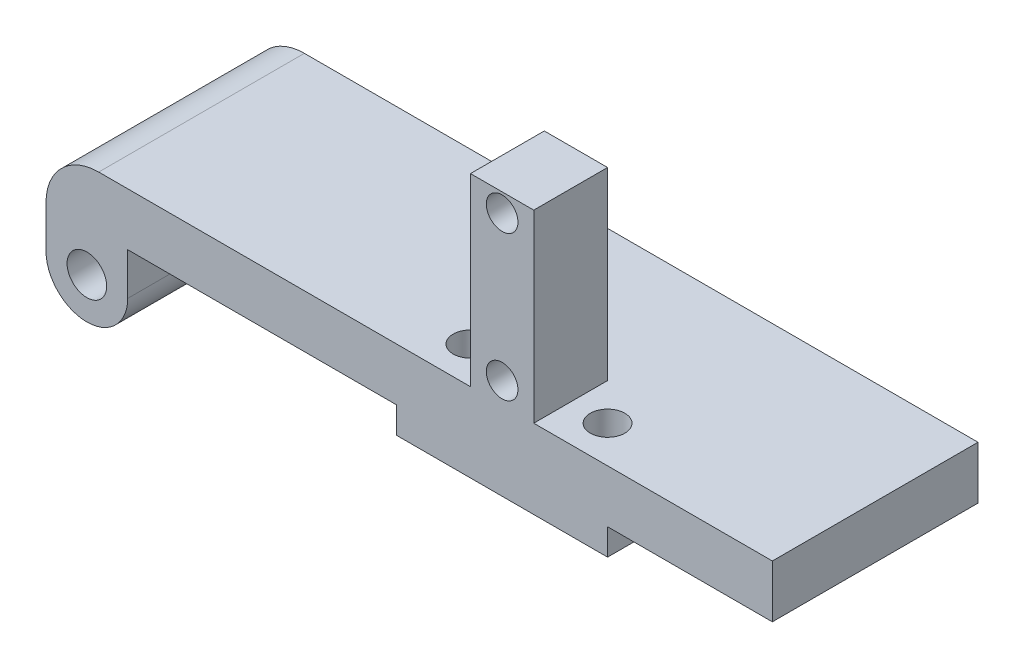
SolidWorks part; units mm, degrees
ref_plane "Front Plane" through (0, 0, 0) normal (0, 0, 1) x (1, 0, 0)
ref_plane "Top Plane" through (0, 0, 0) normal (0, 1, 0) x (1, 0, 0)
ref_plane "Right Plane" through (0, 0, 0) normal (1, 0, 0) x (0, 0, -1)
sketch "Sketch1" plane through (0, 0, 0) normal (0, 0, 1) x (1, 0, 0)
  line L0 (-37.3856, -8.255) -> (-37.3856, -3.175)
  line L1 (-37.3856, 3.175) -> (37.3856, 3.175)
  line L2 (-37.3856, 3.175) -> (-37.3856, -3.175)
  line L3 (-27.5431, -3.175) -> (37.3856, -3.175)
  line L4 (37.3856, 3.175) -> (37.3856, -3.175)
  line L5 (-37.3856, 3.175) -> (37.3856, -3.175) construction
  line L6 (-37.3856, -3.175) -> (37.3856, 3.175) construction
  line L7 (-27.5431, -8.255) -> (-27.5431, -3.175)
  circle A0 centre (-32.4644, -8.255) radius 2.3812
  arc A1 (-37.3856, -8.255) -> (-27.5431, -8.255) centre (-32.4644, -8.255) ccw
  point P0 (0, 0)
  dimension "D1" = 4.7625
  dimension "D3" = 2.54
  dimension "D2" = 6.35
  dimension "D4" = 69.85
  dimension "D5" = 5.08
extrude "Boss-Extrude1" add sketch "Sketch1" along normal blind 38.1
fillet "Fillet1" radius 6.35 1 edges at (-37.3856, 3.175, 19.05)
sketch "Sketch3" plane through (37.3856, 0, 0) normal (1, 0, 0) x (0, 0, -1)
  line L4 (0, -3.175) -> (0, 3.175)
  line L5 (0, 3.175) -> (-38.1, 3.175)
  line L6 (-38.1, 3.175) -> (-38.1, -3.175)
  line L7 (-38.1, -3.175) -> (0, -3.175)
  line L8 (0, -3.175) -> (0, 3.175)
  line L9 (0, 3.175) -> (-38.1, 3.175)
  line L10 (-38.1, 3.175) -> (-38.1, -3.175)
  line L11 (-38.1, -3.175) -> (0, -3.175)
  dimension "D1" = 0
extrude "Boss-Extrude2" add sketch "Sketch3" along normal blind 12.7
sketch "Sketch2" plane through (0, 3.175, 0) normal (0, 1, 0) x (1, 0, 0)
  line L1 (48.4981, -15.875) -> (11.9856, -15.875) construction
  line L2 (48.4981, -15.875) -> (48.4981, 0) construction
  line L3 (48.4981, 0) -> (11.9856, 0) construction
  line L4 (11.9856, -15.875) -> (11.9856, 0) construction
  line L5 (48.4981, -15.875) -> (11.9856, 0) construction
  line L6 (48.4981, 0) -> (11.9856, -15.875) construction
  line L7 (11.9856, -17.4625) -> (-16.5894, -17.4625) construction
  line L8 (11.9856, -17.4625) -> (11.9856, 1.5875) construction
  line L9 (11.9856, 1.5875) -> (-16.5894, 1.5875) construction
  line L10 (-16.5894, -17.4625) -> (-16.5894, 1.5875) construction
  line L11 (11.9856, -17.4625) -> (-16.5894, 1.5875) construction
  line L12 (11.9856, 1.5875) -> (-16.5894, -17.4625) construction
  line L13 (37.3856, -25.4) -> (37.3856, 9.525) construction
  line L14 (50.0856, 0) -> (-31.0356, 0) construction
  line L15 (-34.8456, -38.1) -> (-30.0831, -38.1) construction
  line L16 (-34.8456, -38.1) -> (-30.0831, -38.1) construction
  line L18 (21.3519, -24.765) -> (13.7319, -24.765)
  line L19 (21.3519, -24.765) -> (21.3519, -15.875)
  line L20 (21.3519, -15.875) -> (13.7319, -15.875)
  line L21 (13.7319, -24.765) -> (13.7319, -15.875)
  line L22 (21.3519, -24.765) -> (13.7319, -15.875) construction
  line L23 (21.3519, -15.875) -> (13.7319, -24.765) construction
  point P0 (30.2419, -7.9375)
  point P5 (17.5419, -20.32)
  point P6 (-2.3019, -7.9375)
  point P15 (17.5419, -20.32)
  point P21 (-32.4644, -38.1)
  point P26 (37.3856, -7.9375)
  dimension "Motor_Pos" = 15.875
  dimension "D2" = 36.5125
  dimension "D3" = 28.575
  dimension "D4" = 19.05
  dimension "D5" = 5.5562
  dimension "D6" = 11.1125
  dimension "D7" = 34.925
  dimension "D8" = 69.85
  dimension "D9" = 8.89
  dimension "D10" = 7.62
extrude "Cut-Extrude7" cut sketch "Sketch2" against normal through all
sketch "Sketch10" plane through (0, 3.175, 0) normal (0, 1, 0) x (1, 0, 0)
  line L0 (13.7319, -24.765) -> (13.7319, -15.875) construction
  line L1 (21.3519, -24.765) -> (13.7319, -24.765) construction
  line L2 (21.3519, -24.765) -> (21.3519, -15.875) construction
  line L3 (21.3519, -15.875) -> (13.7319, -15.875) construction
  line L12 (13.7319, -24.765) -> (13.7319, -15.875)
  line L13 (21.3519, -24.765) -> (13.7319, -24.765)
  line L14 (21.3519, -24.765) -> (21.3519, -15.875)
  line L15 (21.3519, -15.875) -> (13.7319, -15.875)
extrude "Boss-Extrude5" add sketch "Sketch10" along normal blind 22.225 and the other way blind 9.525
sketch "Sketch5" plane through (0, 0, 24.765) normal (0, 0, 1) x (1, 0, 0)
  line L0 (17.5419, 25.4) -> (17.5419, -6.35) construction
  line L3 (13.7319, -6.35) -> (21.3519, -6.35) construction
  line L4 (13.7319, 25.4) -> (21.3519, 25.4) construction
  circle A0 centre (17.5419, 5.715) radius 1.905
  circle A1 centre (17.5419, 23.1775) radius 1.905
  point P4 (17.5419, -15.875)
  point P8 (17.5419, 22.225)
  dimension "D1" = 3.81
  dimension "D2" = 17.4625
  dimension "D3" = 12.065
extrude "Cut-Extrude1" cut sketch "Sketch5" against normal through all both and the other way through all
sketch "Sketch6" plane through (0, -3.175, 0) normal (0, 1, 0) x (1, 0, 0)
  line L1 (30.2419, -24.765) -> (4.8419, -24.765)
  line L2 (30.2419, -24.765) -> (30.2419, -15.875)
  line L3 (30.2419, -15.875) -> (4.8419, -15.875)
  line L4 (4.8419, -24.765) -> (4.8419, -15.875)
  line L5 (30.2419, -24.765) -> (4.8419, -15.875) construction
  line L6 (30.2419, -15.875) -> (4.8419, -24.765) construction
  line L9 (4.8419, -24.765) -> (30.2419, -24.765) construction
  line L11 (21.3519, -15.875) -> (13.7319, -15.875) construction
  line L12 (21.3519, -24.765) -> (13.7319, -24.765) construction
  line L13 (21.3519, -24.765) -> (13.7319, -24.765)
  line L14 (13.7319, -24.765) -> (13.7319, -15.875) construction
  point P0 (17.5419, -20.32)
  point P5 (0, 0)
  point P10 (30.5209, -24.765)
  point P14 (17.5419, -24.765)
  point P16 (17.5419, -24.765)
  line M22 (13.7319, -15.875) -> (13.7319, -24.765)
  line M24 (21.3519, -24.765) -> (21.3519, -15.875)
  dimension "D1" = 25.4
  dimension "D2" = 8.89
  dimension "D3" = 8.89
extrude "Boss-Extrude4" add sketch "Sketch6" against normal up to surface (3.175 mm away) contours L1 L4 L3 M22 | L3 L2 L1 M24 region at (25.7969, -3.175, 20.32) region at (9.2869, -3.175, 20.32) up to face at (17.5419, -6.35, 20.32)
sketch "Sketch7" plane through (0, -6.35, 0) normal (0, -1, 0) x (-1, 0, 0)
  line L1 (-4.8419, -24.765) -> (-13.7319, -24.765) construction
  line L2 (-4.8419, -24.765) -> (-4.8419, -15.875) construction
  line L3 (-4.8419, -15.875) -> (-13.7319, -15.875) construction
  line L4 (-13.7319, -24.765) -> (-13.7319, -15.875) construction
  line L5 (-4.8419, -24.765) -> (-13.7319, -15.875) construction
  line L6 (-4.8419, -15.875) -> (-13.7319, -24.765) construction
  line L10 (-17.5419, -24.765) -> (-17.5419, -15.875) construction
  line L12 (-4.8419, -24.765) -> (-30.2419, -24.765) construction
  line L13 (-30.2419, -15.875) -> (-4.8419, -15.875) construction
  line L14 (-4.8419, -24.765) -> (-4.8419, -15.875) construction
  line L15 (-21.3519, -24.765) -> (-21.3519, -15.875) construction
  line L16 (-13.7319, -24.765) -> (-21.3519, -24.765) construction
  line L17 (-13.7319, -15.875) -> (-13.7319, -24.765) construction
  line L18 (-21.3519, -15.875) -> (-13.7319, -15.875) construction
  line L19 (-21.3519, -24.765) -> (-21.3519, -15.875) construction
  line L20 (-13.7319, -24.765) -> (-21.3519, -24.765) construction
  line L21 (-13.7319, -15.875) -> (-13.7319, -24.765) construction
  line L22 (-21.3519, -15.875) -> (-13.7319, -15.875) construction
  circle A0 centre (-9.2869, -20.32) radius 2.0828
  circle A2 centre (-25.7969, -20.32) radius 2.0828
  point P7 (-17.5419, -15.875)
  point P10 (-17.5419, -24.765)
  point P13 (-26.6911, -20.8711)
  point P14 (-17.5419, -24.765)
  point P22 (-14.7292, -15.875)
  point P23 (-26.2619, -20.8913)
  point P27 (0, 0)
  dimension "D1" = 4.1656
extrude "Cut-Extrude2" cut sketch "Sketch7" against normal through all both and the other way through all
ref_plane "Plane1" through (-27.5431, -3.175, 38.1) normal (1, 0, 0) x (0, 0, -1)
sketch "Sketch9" plane through (0, 0, 38.1) normal (0, 0, 1) x (1, 0, 0)
  line L0 (50.0856, 3.175) -> (50.0856, -3.175) construction
  line L1 (-27.5431, -3.175) -> (50.0856, -3.175) construction
  line L2 (-27.5431, -8.255) -> (-27.5431, -3.175) construction
  line L3 (-37.3856, -3.175) -> (-37.3856, -8.255) construction
  line L4 (50.0856, 3.175) -> (-31.0356, 3.175) construction
  line L5 (50.0856, 3.175) -> (50.0856, -3.175)
  line L6 (-27.5431, -3.175) -> (50.0856, -3.175)
  line L7 (-27.5431, -8.255) -> (-27.5431, -3.175)
  line L8 (-37.3856, -3.175) -> (-37.3856, -8.255)
  line L9 (50.0856, 3.175) -> (-31.0356, 3.175)
  arc A0 (-37.3856, -8.255) -> (-27.5431, -8.255) centre (-32.4644, -8.255) ccw construction
  arc A1 (-31.0356, 3.175) -> (-37.3856, -3.175) centre (-31.0356, -3.175) ccw construction
  arc A2 (-37.3856, -8.255) -> (-27.5431, -8.255) centre (-32.4644, -8.255) ccw
  arc A3 (-31.0356, 3.175) -> (-37.3856, -3.175) centre (-31.0356, -3.175) ccw
extrude "Cut-Extrude8" cut sketch "Sketch9" against normal up to surface (13.335 mm away) up to face at (19.4469, 5.715, 24.765)
